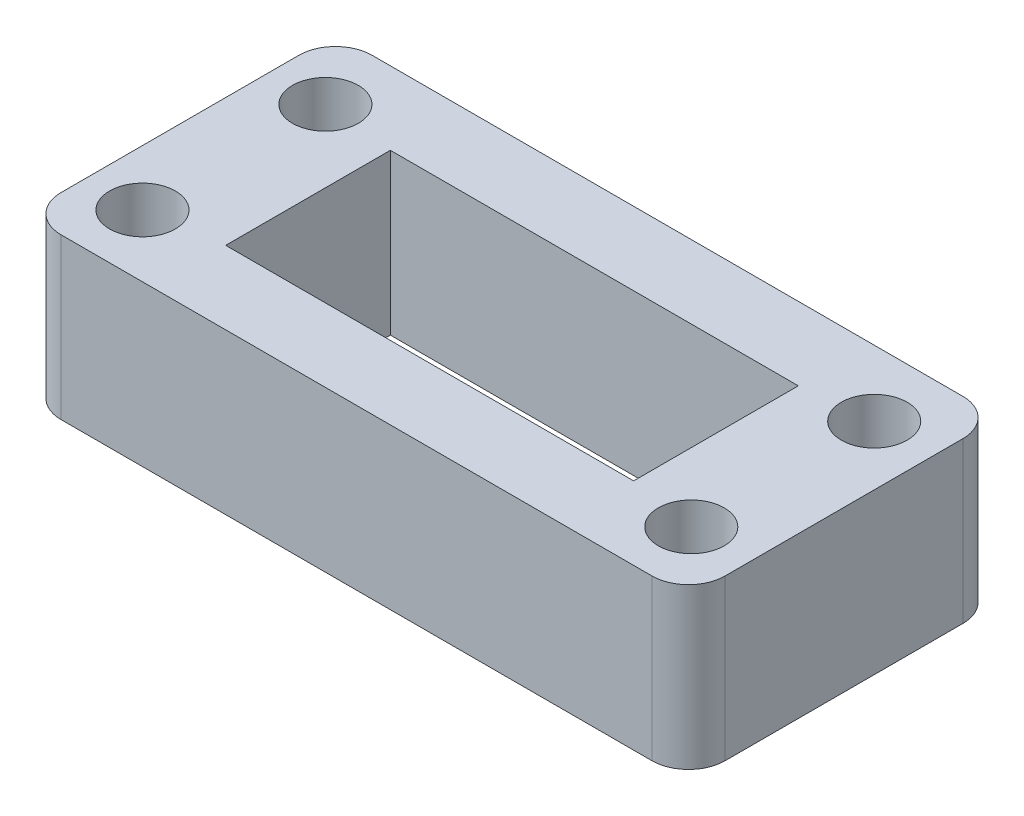
SolidWorks part; units mm, degrees
ref_plane "Front Plane" through (0, 0, 0) normal (0, 0, 1) x (1, 0, 0)
ref_plane "Top Plane" through (0, 0, 0) normal (0, 1, 0) x (1, 0, 0)
ref_plane "Right Plane" through (0, 0, 0) normal (1, 0, 0) x (0, 0, -1)
sketch "Sketch1" plane through (0, 0, 0) normal (0, 1, 0) x (1, 0, 0)
  line L0 (0, 0) -> (36.3, 0)
  line L1 (36.3, 0) -> (36.3, 17)
  line L2 (36.3, 17) -> (0, 17)
  line L3 (0, 17) -> (0, 0)
  line L4 (7, 13) -> (7, 4)
  line L5 (7, 4) -> (29.3, 4)
  line L6 (29.3, 4) -> (29.3, 13)
  line L7 (29.3, 13) -> (7, 13)
  line L8 (0, 8.5) -> (36.3, 8.5) construction
  line L9 (18.15, 0) -> (18.15, 17) construction
  point P13 (18.15, 13)
  point P14 (29.3, 8.5)
  point P15 (47.4451, 0)
  dimension "D1" = 7
  dimension "D2" = 4
  dimension "D3" = 36.3
  dimension "D4" = 17
extrude "Boss-Extrude1" add sketch "Sketch1" along normal blind 8.75
sketch "Sketch2" plane through (0, 8.75, 0) normal (0, 1, 0) x (1, 0, 0)
  point P0 (3.05, 3.4)
  point P6 (33.05, 3.4)
  point P9 (33.05, 13.4)
  point P15 (3.05, 13.4)
hole_wizard "M3 Clearance Hole1" positions "Sketch2" profile "Sketch3" hole size "M3" standard "ANSI Metric" end condition through all
sketch "Sketch3" plane through (3.05, 8.75, -3.4) normal (1, 0, 0) x (0, 0, 1)
  line L0 (0, 0) -> (0, 8.75)
  line L1 (0, 8.75) -> (1.8, 8.75)
  line L2 (1.8, 8.75) -> (1.8, 0)
  line L5 (1.8, 0) -> (0, 0)
  line L11 (0, -6.35) -> (0, 107.95) construction
  dimension "Thru Hole Dia." = 3.6
  dimension "Thru Hole Depth" = 8.75
fillet "Fillet1" radius 2 4 edges at (0, 4.375, -17) (36.3, 4.375, -17) (36.3, 4.375, 0) (0, 4.375, 0)
